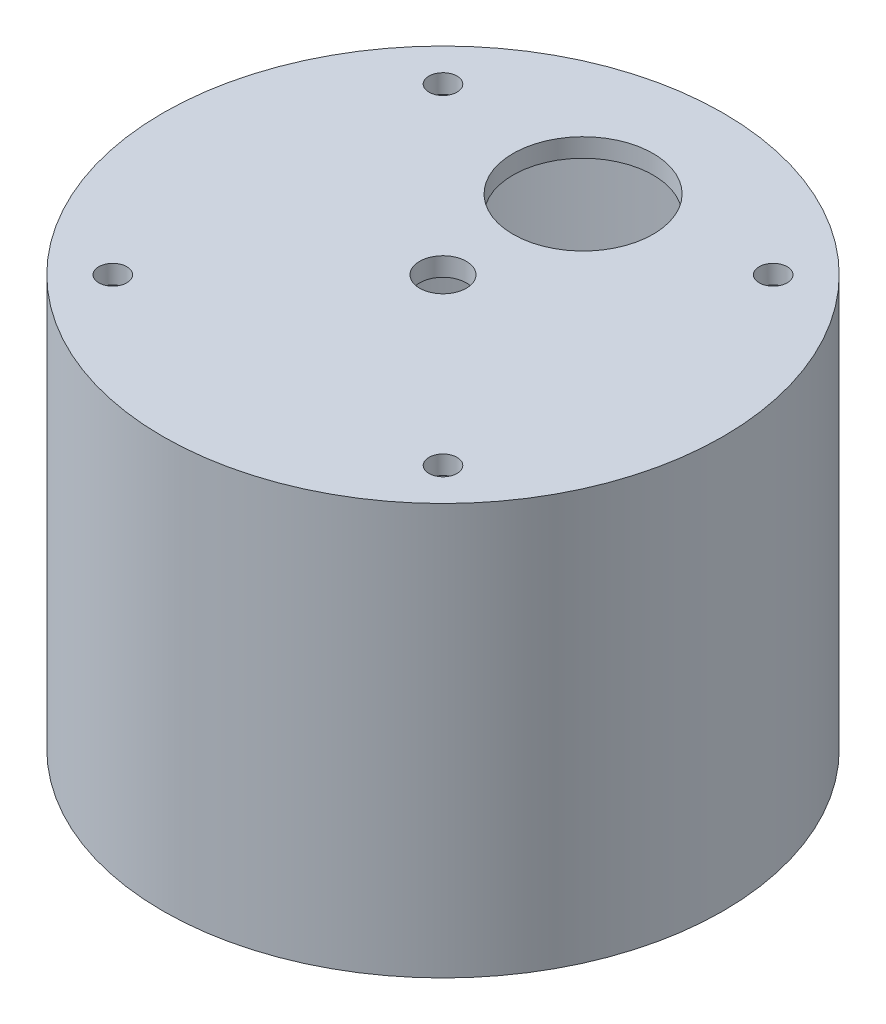
SolidWorks part; units mm, degrees
ref_plane "Front Plane" through (0, 0, 0) normal (0, 0, 1) x (1, 0, 0)
ref_plane "Top Plane" through (0, 0, 0) normal (0, 1, 0) x (1, 0, 0)
ref_plane "Right Plane" through (0, 0, 0) normal (1, 0, 0) x (0, 0, -1)
sketch "Sketch1" plane through (0, 0, 0) normal (0, 1, 0) x (1, 0, 0)
  circle A0 centre (0, 0) radius 30
  dimension "D1" = 60
extrude "Boss-Extrude1" add sketch "Sketch1" along normal blind 2
sketch "Sketch2" plane through (0, 2, 0) normal (0, 1, 0) x (1, 0, 0)
  circle A0 centre (0, 0) radius 30
  circle A1 centre (0, 0) radius 29
  dimension "D1" = 58
  dimension "D2" = 60
extrude "Boss-Extrude2" add sketch "Sketch2" along normal blind 40
sketch "Sketch3" plane through (0, 42, 0) normal (0, 1, 0) x (1, 0, 0)
  circle A0 centre (0, 0) radius 30
  dimension "D1" = 60
extrude "Boss-Extrude3" add sketch "Sketch3" along normal blind 2
sketch "Sketch4" plane through (0, 44, 0) normal (0, 1, 0) x (1, 0, 0)
  circle A0 centre (0, 15) radius 7.5
  dimension "D1" = 15
  dimension "D2" = 15
extrude "Cut-Extrude1" cut sketch "Sketch4" against normal through all
sketch "Sketch8" plane through (0, 44, 0) normal (0, 1, 0) x (1, 0, 0)
  line L0 (-21.2132, 21.2132) -> (21.2132, -21.2132) construction
  line L1 (-30, 0) -> (30, 0) construction
  line L2 (-21.2132, -21.2132) -> (21.2132, 21.2132) construction
  circle A0 centre (0, 0) radius 30 construction
  circle A1 centre (-17.6777, 17.6777) radius 1.5
  circle A2 centre (17.6777, -17.6777) radius 1.5
  circle A3 centre (17.6777, 17.6777) radius 1.5
  circle A4 centre (-17.6777, -17.6777) radius 1.5
  point P7 (0, 0)
  point P16 (0, 0)
  dimension "D1" = 3
  dimension "D2" = 25
  dimension "D3" = 3
  dimension "D4" = 25
  dimension "D5" = 45
extrude "Cut-Extrude4" cut sketch "Sketch8" against normal through all
sketch "Sketch9" plane through (0, 44, 0) normal (0, 1, 0) x (1, 0, 0)
  circle A0 centre (0, 0) radius 2.5
  dimension "D1" = 5
extrude "Cut-Extrude5" cut sketch "Sketch9" against normal through all
